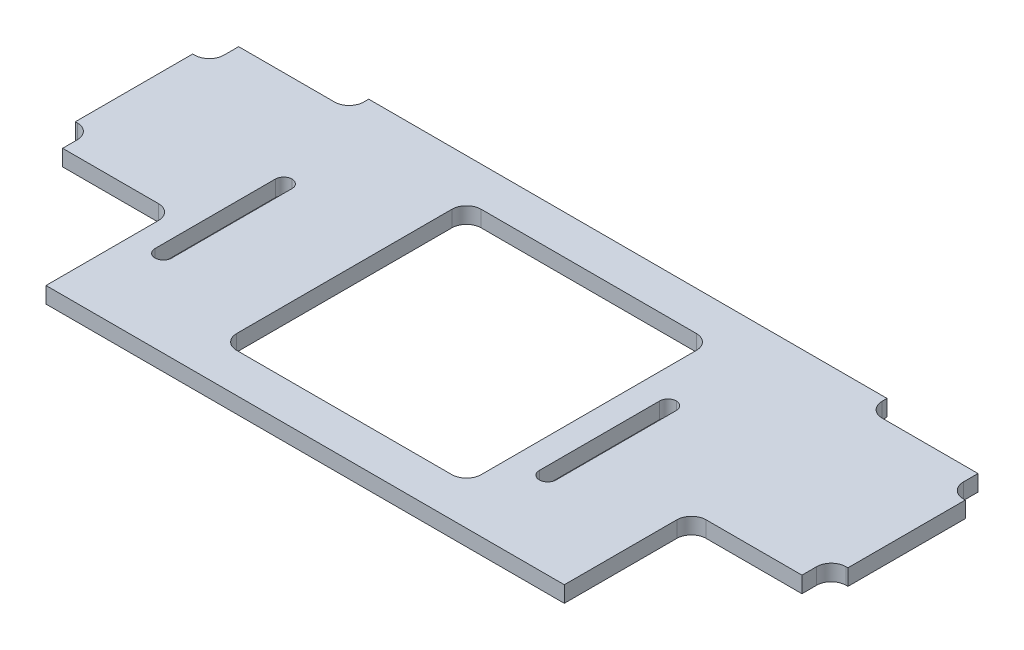
SolidWorks part; units mm, degrees
material "PVC hart"
ref_plane "Ebene vorne" through (0, 0, 0) normal (0, 0, 1) x (1, 0, 0)
ref_plane "Ebene oben" through (0, 0, 0) normal (0, 1, 0) x (1, 0, 0)
ref_plane "Ebene rechts" through (0, 0, 0) normal (1, 0, 0) x (0, 0, -1)
sketch "Skizze1" plane through (0, 0, 0) normal (0, 1, 0) x (1, 0, 0)
  line L0 (26.5, 18) -> (-26.5, 18)
  line L1 (26.5, -15) -> (-26.5, -15)
  line L2 (0, 18) -> (0, 14) construction
  line L3 (0, 14) -> (0, -11) construction
  line L4 (0, -11) -> (0, -15) construction
  line L5 (-22.5, 0) -> (15.1, 0) construction
  line L6 (-26.5, 16) -> (-37.8, 16)
  line L7 (-12.5, 14) -> (12.5, 14)
  line L8 (-12.5, 14) -> (-12.5, -11)
  line L9 (-12.5, -11) -> (12.5, -11)
  line L10 (12.5, 14) -> (12.5, -11)
  line L11 (-37.8, 16) -> (-37.8, 13)
  line L12 (-37.8, 13) -> (-39.5, 13)
  line L13 (-39.5, 13) -> (-39.5, 1)
  line L14 (16.8, -7) -> (15.1, -7)
  line L15 (16.8, -7) -> (16.8, 7)
  line L16 (16.8, 7) -> (15.1, 7)
  line L17 (15.1, -7) -> (15.1, 7)
  line L18 (-39.5, 1) -> (-37.8, 1)
  line L19 (-22.5, -7) -> (-22.5, 7)
  line L20 (-24.2, 7) -> (-22.5, 7)
  line L21 (-24.2, -7) -> (-24.2, 7)
  line L22 (-24.2, -7) -> (-22.5, -7)
  line L23 (-37.8, 1) -> (-37.8, -2)
  line L24 (-37.8, -2) -> (-26.5, -2)
  line L26 (37.8, -2) -> (26.5, -2)
  line L27 (39.5, 1) -> (37.8, 1)
  line L28 (37.8, 1) -> (37.8, -2)
  line L29 (-26.5, -15) -> (-26.5, 18)
  line L30 (26.5, -15) -> (26.5, 18)
  line L31 (39.5, 13) -> (39.5, 1)
  line L32 (37.8, 13) -> (39.5, 13)
  line L33 (37.8, 16) -> (37.8, 13)
  line L34 (26.5, 16) -> (37.8, 16)
  point P28 (-39.5, 7)
  dimension "D2" = 11
  dimension "D3" = 14
  dimension "D4" = 22.5
  dimension "D5" = 25
  dimension "D6" = 1.7
  dimension "D7" = 4
  dimension "D8" = 1.7
  dimension "D9" = 12
  dimension "D10" = 53
  dimension "D11" = 18
  dimension "D12" = 79
  dimension "D13" = 22
  dimension "D14" = 21
extrude "Aufsatz-Linear austragen1" add sketch "Skizze1" against normal mid plane 1.65 contours L30 L0 L29 L1 L14 L17 L16 L15 L7 L10 L9 L8 L22 L21 L20 L19 | L24 L29 L6 L11 L12 L13 L18 L23 | L34 L30 L26 L28 L27 L31 L32 L33 region at (25.8757, 0, -17) region at (32.7425, 0, -7) region at (-32.7425, 0, -7)
fillet "Verrundung1" radius 1.5 12 edges at (12.5, 0, -14) (12.5, 0, 11) (-12.5, 0, 11) (-12.5, 0, -14) (26.5, 0, -16) (26.5, 0, 2) (-26.5, 0, 2) (-26.5, 0, -16) (37.8, 0, -13) (37.8, 0, -1) (-37.8, 0, -1) (-37.8, 0, -13)
fillet "Verrundung2" radius 0.85 8 edges at (15.1, 0, 7) (16.8, 0, 7) (15.1, 0, -7) (16.8, 0, -7) (-24.2, 0, 7) (-22.5, 0, 7) (-22.5, 0, -7) (-24.2, 0, -7)
ref_plane "Ebene1" through (0, 0, -7) normal (0, 0, -1) x (-1, 0, 0)
